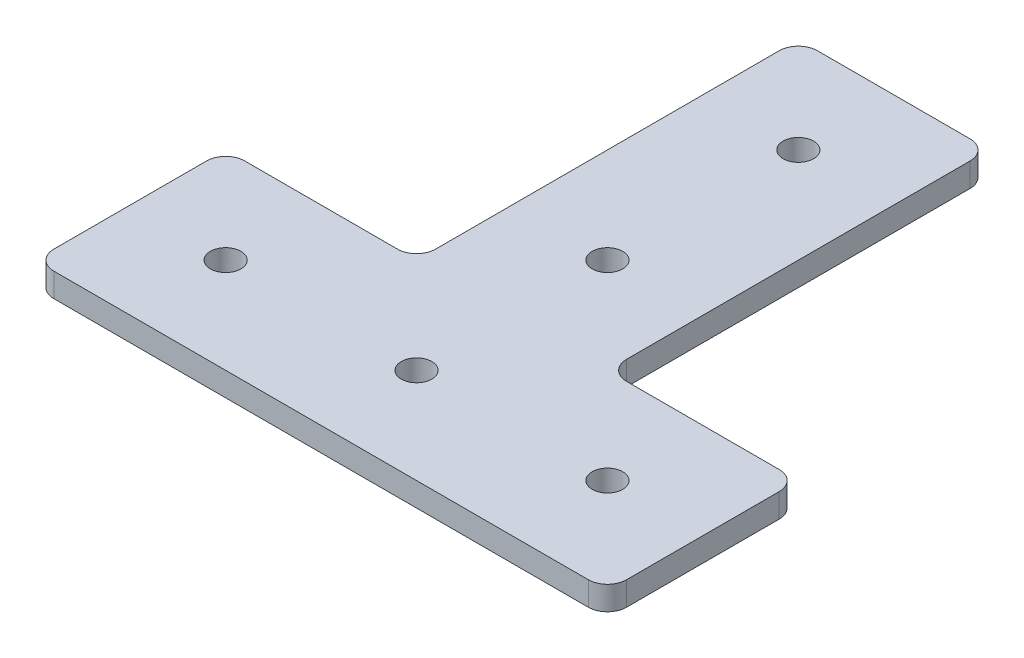
SolidWorks part; units mm, degrees
material "3.0205 (EN-AW 1200)"
ref_plane "Front Plane" through (0, 0, 0) normal (0, 0, 1) x (1, 0, 0)
ref_plane "Top Plane" through (0, 0, 0) normal (0, 1, 0) x (1, 0, 0)
ref_plane "Right Plane" through (0, 0, 0) normal (1, 0, 0) x (0, 0, -1)
sketch "Sketch1" plane through (0, 0, 0) normal (0, 1, 0) x (1, 0, 0)
  line L0 (18.7205, 17.4957) -> (39.0405, 17.4957)
  line L1 (-32.0795, 17.4957) -> (-11.7595, 17.4957)
  line L2 (-34.6195, 14.9557) -> (-34.6195, -5.3643)
  line L3 (-32.0795, -7.9043) -> (39.0405, -7.9043)
  line L4 (41.5805, 14.9557) -> (41.5805, -5.3643)
  line L10 (-9.2195, 20.0357) -> (-9.2195, 65.7557)
  line L11 (-6.6795, 68.2957) -> (13.6405, 68.2957)
  line L12 (16.1805, 20.0357) -> (16.1805, 65.7557)
  circle A0 centre (3.4805, 4.7957) radius 2.032
  circle A1 centre (-21.9195, 4.7957) radius 2.032
  circle A2 centre (28.8805, 4.7957) radius 2.032
  circle A3 centre (3.4805, 30.1957) radius 2.032
  circle A4 centre (3.4805, 55.5957) radius 2.032
  arc A5 (16.1805, 65.7557) -> (13.6405, 68.2957) centre (13.6405, 65.7557) ccw
  arc A6 (-9.2195, 65.7557) -> (-6.6795, 68.2957) centre (-6.6795, 65.7557) cw
  arc A7 (-11.7595, 17.4957) -> (-9.2195, 20.0357) centre (-11.7595, 20.0357) ccw
  arc A8 (16.1805, 20.0357) -> (18.7205, 17.4957) centre (18.7205, 20.0357) ccw
  arc A9 (39.0405, 17.4957) -> (41.5805, 14.9557) centre (39.0405, 14.9557) cw
  arc A10 (41.5805, -5.3643) -> (39.0405, -7.9043) centre (39.0405, -5.3643) cw
  arc A11 (-32.0795, -7.9043) -> (-34.6195, -5.3643) centre (-32.0795, -5.3643) cw
  arc A12 (-34.6195, 14.9557) -> (-32.0795, 17.4957) centre (-32.0795, 14.9557) cw
  point P20 (16.1805, 68.2957)
  point P23 (-9.2195, 68.2957)
  point P28 (16.1805, 17.4957)
  point P31 (41.5805, 17.4957)
  point P34 (41.5805, -7.9043)
  point P37 (-34.6195, -7.9043)
  dimension "D6" = 4.064
  dimension "D7" = 12.7
  dimension "D8" = 12.7
  dimension "D9" = 4.064
  dimension "D10" = 4.064
  dimension "D11" = 12.7
  dimension "D12" = 25.4
  dimension "D13" = 25.4
  dimension "D14" = 12.7
  dimension "D15" = 4.064
  dimension "D16" = 25.4
  dimension "D17" = 12.7
  dimension "D18" = 4.064
  dimension "D19" = 25.4
  dimension "D20" = 2.54
  dimension "D1" = 76.2
  dimension "D2" = 25.4
  dimension "D3" = 50.8
  dimension "D4" = 25.4
  dimension "D5" = 25.4
extrude "Boss-Extrude1" add sketch "Sketch1" along normal blind 3.175
